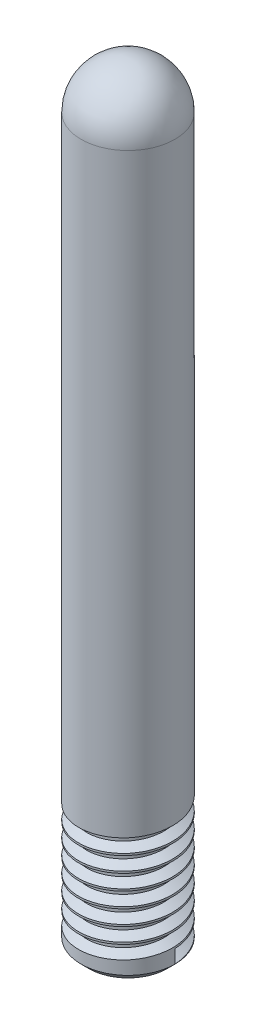
SolidWorks part; units mm, degrees
ref_plane "Front Plane" through (0, 0, 0) normal (0, 0, 1) x (1, 0, 0)
ref_plane "Top Plane" through (0, 0, 0) normal (0, 1, 0) x (1, 0, 0)
ref_plane "Right Plane" through (0, 0, 0) normal (1, 0, 0) x (0, 0, -1)
sketch "Rod Sketch" plane through (0, 0, 0) normal (0, 0, 1) x (1, 0, 0)
  line L0 (0, 0) -> (0, 25) construction
  line L1 (0, 0) -> (1.525, 0)
  line L2 (1.525, 0) -> (1.525, 23.475)
  line L3 (0, 0) -> (0, 25)
  arc A0 (0, 25) -> (1.525, 23.475) centre (0, 23.475) cw
  dimension "D1" = 3.05
  dimension "D2" = 25
revolve "Rod Revolve" add sketch "Rod Sketch" angle 360 about L0
chamfer "Chamfur Before Thread" distance 0.25 1 edges at (0, 0, -1.525)
ref_plane "Plane1" through (0, 4, 0) normal (0, 1, 0) x (1, 0, 0)
thread "Thread2" pitch 0.5 method cut profile "Thread Profile2" start angle 0, offset 0, length 0, pitch 0.5, diameter 3.05
ref_plane "Plane3" through (1.525, 0.25, 0) normal (0, 0, 1) x (1, 0, 0)
sketch "Thread Profile2" plane through (1.525, 0.25, 0) normal (0, 0, 1) x (1, 0, 0)
  line L0 (0, 0) -> (0, 0.5) construction
  line L11 (0, 0) -> (0, 0.4375)
  line L12 (0, 0.4375) -> (-0.2706, 0.2812)
  line L13 (-0.2706, 0.2812) -> (-0.2706, 0.1562)
  line L15 (-0.2706, 0.1562) -> (0, 0)
  line L17 (-0.2706, 0.2187) -> (0, 0.2187) construction
  point P2 (0, 0)
  dimension "Pitch" = 0.5
  dimension "Profile_Angle" = 60
  dimension "Profile_Land" = 0.125
  dimension "Profile_Height" = 0.2706
